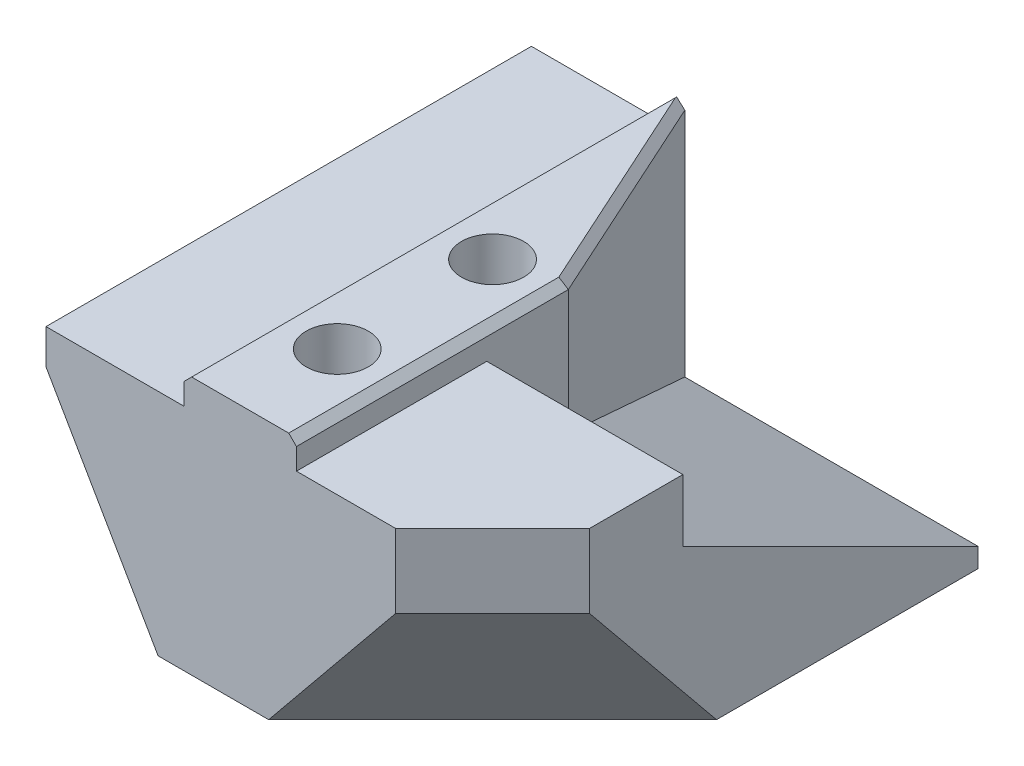
SolidWorks part; units mm, degrees
ref_plane "前视基准面" through (0, 0, 0) normal (0, 0, 1) x (1, 0, 0)
ref_plane "上视基准面" through (0, 0, 0) normal (0, 1, 0) x (1, 0, 0)
ref_plane "右视基准面" through (0, 0, 0) normal (1, 0, 0) x (0, 0, -1)
other "Configuration Table"
sketch "草图1" plane through (0, 0, 0) normal (0, 1, 0) x (1, 0, 0)
  line L1 (0, 0) -> (20, 0)
  line L2 (0, 0) -> (0, 20)
  line L3 (0, 20) -> (20, 20)
  line L4 (20, 0) -> (20, 20)
  dimension "D1" = 20
  dimension "D2" = 20
extrude "凸台-拉伸1" add sketch "草图1" along normal blind 4
sketch "草图2" plane through (0, 4, 0) normal (0, 1, 0) x (1, 0, 0)
  line L0 (0, 0) -> (20, 0) construction
  line L1 (0, 20) -> (12.9, 20)
  line L2 (0, 20) -> (0, 0)
  line L3 (0, 0) -> (12.9, 0)
  line L4 (12.9, 20) -> (12.9, 0)
  line L5 (20, 0) -> (20, 20) construction
  dimension "D1" = 7.1
extrude "凸台-拉伸2" add sketch "草图2" along normal blind 3.8
sketch "草图3" plane through (0, 0, 0) normal (0, -1, 0) x (-1, 0, 0)
  line L0 (0, 20) -> (0, 0) construction
  line L2 (0, 0) -> (-20, 0) construction
  circle A0 centre (-10, 5) radius 1.6
  circle A1 centre (-10, 13) radius 1.6
  dimension "D1" = 3.2
  dimension "D3" = 5
  dimension "D2" = 10
  dimension "D4" = 2
extrude "切除-拉伸1" cut sketch "草图3" against normal through all
sketch "草图4" plane through (0, 7.8, 0) normal (0, 1, 0) x (1, 0, 0)
  line L0 (12.9, 20) -> (0, 20) construction
  line L1 (7.1, 20) -> (12.9, 20)
  line L2 (7.1, 20) -> (7.1, 0)
  line L3 (7.1, 0) -> (12.9, 0)
  line L4 (12.9, 20) -> (12.9, 0)
  line L5 (0, 20) -> (0, 0) construction
  circle A0 centre (10, 13) radius 1.6
  circle A1 centre (10, 5) radius 1.6
  point P6 (10, 20)
  dimension "D1" = 5.8
  dimension "D2" = 10
extrude "凸台-拉伸3" add sketch "草图4" along normal blind 1.5
sketch "草图5" plane through (0, 0, 0) normal (0, -1, 0) x (-1, 0, 0)
  circle A0 centre (-10, 5) radius 3
  circle A1 centre (-10, 13) radius 3
  dimension "D1" = 6
  dimension "D2" = 6
extrude "切除-拉伸3" cut sketch "草图5" against normal blind 2.4
sketch "草图6" plane through (20, 0, 0) normal (1, 0, 0) x (0, 0, -1)
  line L1 (20, 0) -> (0, 0)
  line L2 (20, 0) -> (20, 4)
  line L3 (20, 4) -> (0, 4)
  line L4 (0, 0) -> (0, 4)
extrude "凸台-拉伸4" add sketch "草图6" along normal blind 3
sketch "草图7" plane through (0, 0, 0) normal (0, -1, 0) x (-1, 0, 0)
  line L1 (-23, 20) -> (0, 20)
  line L2 (-23, 20) -> (-23, 0)
  line L3 (-23, 0) -> (0, 0)
  line L4 (0, 20) -> (0, 0)
  circle A0 centre (-10, 13) radius 3
  circle A1 centre (-10, 5) radius 3
extrude "凸台-拉伸5" add sketch "草图7" along normal blind 4
sketch "草图9" plane through (0, 4, 0) normal (0, 1, 0) x (1, 0, 0)
  line L1 (23, 20) -> (12.9, 20)
  line L2 (23, 20) -> (23, 0)
  line L3 (23, 0) -> (12.9, 0)
  line L4 (12.9, 20) -> (12.9, 0)
extrude "凸台-拉伸6" add sketch "草图9" along normal blind 2
sketch "草图11" plane through (0, 0, -20) normal (0, 0, -1) x (-1, 0, 0)
  line L20 (-23, 6) -> (-23, -4)
  line L21 (-23, -4) -> (0, -4)
  line L22 (0, -4) -> (0, 7.8)
  line L23 (0, 7.8) -> (-7.1, 7.8)
  line L24 (-7.1, 7.8) -> (-7.1, 9.3)
  line L25 (-7.1, 9.3) -> (-12.9, 9.3)
  line L26 (-12.9, 9.3) -> (-12.9, 6)
  line L29 (-12.9, 6) -> (-23, 6)
  line L30 (-23, 6) -> (-23, -4)
  line L31 (-23, -4) -> (0, -4)
  line L32 (0, -4) -> (0, 7.8)
  line L33 (0, 7.8) -> (-7.1, 7.8)
  line L34 (-7.1, 7.8) -> (-7.1, 9.3)
  line L35 (-7.1, 9.3) -> (-12.9, 9.3)
  line L36 (-12.9, 9.3) -> (-12.9, 6)
  line L39 (-12.9, 6) -> (-23, 6)
  dimension "D1" = 0
extrude "凸台-拉伸7" add sketch "草图11" along normal blind 5
chamfer "倒角7" distance 10 angle 30 1 edges at (0, -4, -12.5) first distance on face at (0, 1.9, -12.5)
chamfer "倒角8" distance 5 angle 45 1 edges at (23, 1, 0)
chamfer "倒角9" distance 8 angle 30 1 edges at (20.5, -4, -2.5) first distance on face at (20.5, 1, -2.5)
sketch "草图15" plane through (23, 0, 0) normal (1, 0, 0) x (0, 0, -1)
  line L0 (25, -3) -> (25, 6)
  line L1 (25, 6) -> (25, -4) construction
  line L2 (25, 6) -> (7, 6)
  line L3 (25, 6) -> (0, 6) construction
  line L4 (7, 6) -> (25, -3)
  dimension "D1" = 9
  dimension "D2" = 18
extrude "切除-拉伸9" cut sketch "草图15" against normal up to surface (10.1 mm away) up to face at (12.9, 7.65, -12.5)
sketch "草图16" plane through (0, 9.3, 0) normal (0, 1, 0) x (1, 0, 0)
  line L0 (7.9, 25) -> (12.9, 25)
  line L1 (7.1, 25) -> (12.9, 25) construction
  line L2 (12.9, 7) -> (12.9, 25) construction
  line L3 (12.9, 0) -> (12.9, 25) construction
  line L4 (12.9, 25) -> (12.9, 14)
  line L5 (12.9, 14) -> (7.9, 25)
  dimension "D1" = 5
  dimension "D2" = 11
extrude "切除-拉伸10" cut sketch "草图16" against normal up to surface (6.8 mm away) up to face at (17.95, 1.5, -16)
chamfer "倒角10" distance 1.5 angle 45 2 edges at (10, 2.4, -14.6) (10, 2.4, -6.6)
chamfer "倒角11" distance 0.4 angle 45 3 edges at (10.4, 9.3, -19.5) (12.9, 9.3, -7) (7.1, 9.3, -12.5)
sketch "草图17" plane through (0, 6, 0) normal (0, 1, 0) x (1, 0, 0)
  line L5 (23, 5) -> (23, 7)
  line L6 (23, 7) -> (12.9, 7)
  line L7 (12.9, 7) -> (12.9, 0)
  line L8 (12.9, 0) -> (18, 0)
  line L9 (18, 0) -> (23, 5)
  line L10 (23, 5) -> (23, 7)
  line L11 (23, 7) -> (12.9, 7)
  line L12 (12.9, 7) -> (12.9, 0)
  line L13 (12.9, 0) -> (18, 0)
  line L14 (18, 0) -> (23, 5)
  dimension "D1" = 0
extrude "凸台-拉伸8" add sketch "草图17" along normal blind 1.8
sketch "草图19" plane through (23, 0, 0) normal (1, 0, 0) x (0, 0, -1)
  line L0 (7, 7.8) -> (17.6507, 7.8)
  line L1 (9.8, 7.8) -> (9.8, 4.6)
  line L2 (7, 6) -> (25, -3) construction
  line L3 (9.8, 4.6) -> (7, 6)
  line L4 (7, 6) -> (7, 7.8)
  line M2 (25, -3) -> (7, 6)
  line M3 (7, 6) -> (7, 7.8)
  dimension "D1" = 3.2
extrude "凸台-拉伸10" add sketch "草图19" against normal up to surface (10.1 mm away) contours L1 L0 M3 M2 region at (23, 6.5173, -8.5307) up to face at (12.9, 6.9833, -7)
